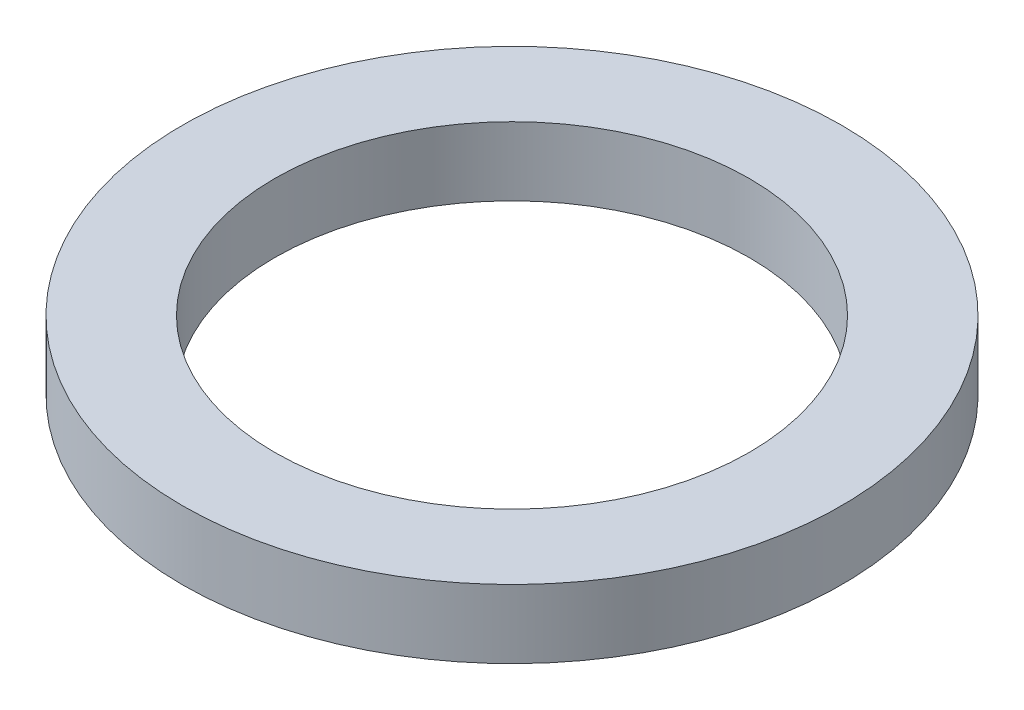
SolidWorks part; units mm, degrees
ref_plane "Front Plane" through (0, 0, 0) normal (0, 0, 1) x (1, 0, 0)
ref_plane "Top Plane" through (0, 0, 0) normal (0, 1, 0) x (1, 0, 0)
ref_plane "Right Plane" through (0, 0, 0) normal (1, 0, 0) x (0, 0, -1)
sketch "Sketch1" plane through (0, 0, 0) normal (0, 1, 0) x (1, 0, 0)
  circle A0 centre (0, 0) radius 62.5
  dimension "FLANGE_OD" = 125
extrude "Boss-Extrude1" add sketch "Sketch1" along normal blind 13
sketch "Sketch2" plane through (0, 0, 0) normal (0, 1, 0) x (1, 0, 0)
  circle A0 centre (0, 0) radius 45
  dimension "BORE_D" = 90
extrude "Cut-Extrude1" cut sketch "Sketch2" along normal through all
sketch "Sketch3" plane through (0, 13, 0) normal (0, 1, 0) x (1, 0, 0)
  circle A0 centre (0, 0) radius 26.1905 construction
  circle A1 centre (-26.1905, 0) radius 2.7075
  dimension "BOLT_D" = 5.4149
  dimension "BOLT_PCD" = 52.381
extrude "Cut-Extrude2" cut sketch "Sketch3" against normal blind 9.4798 rebuild error yes
pattern_circular "CirPattern1" count 4 over 360 rebuild error yes
